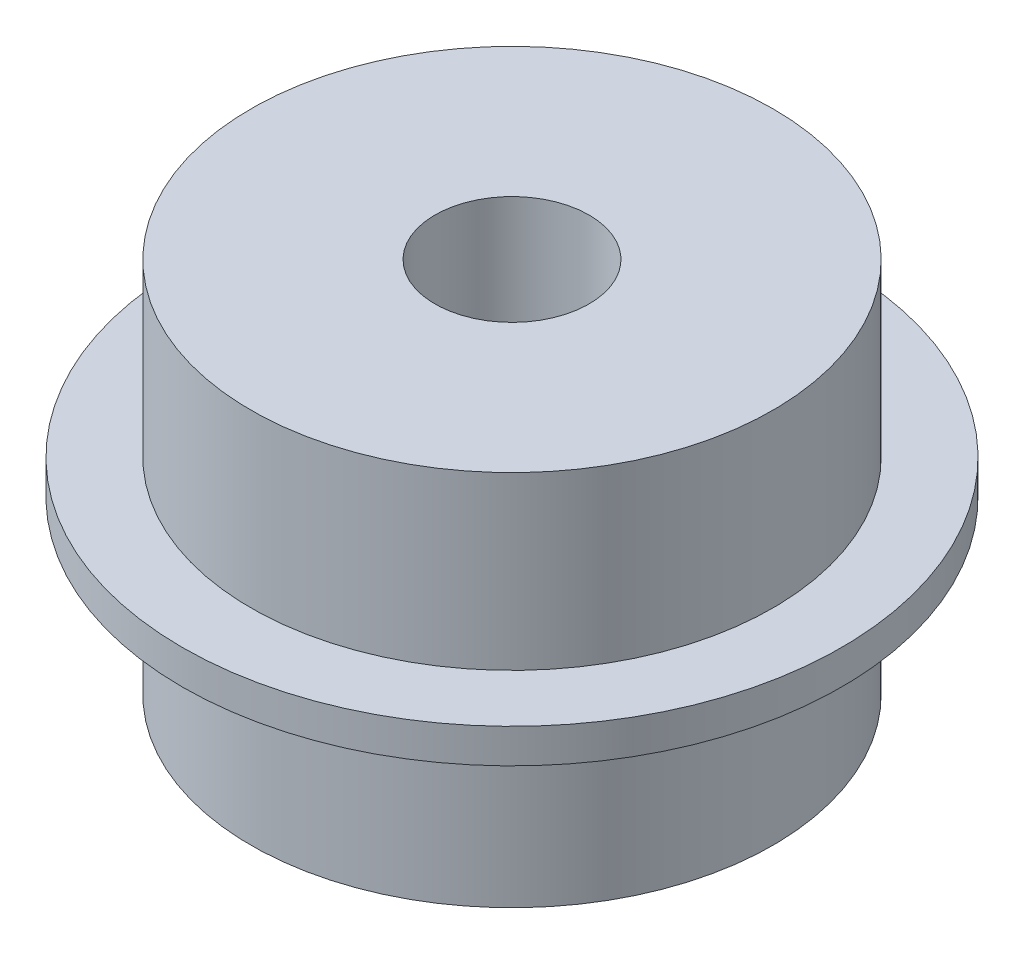
SolidWorks part; units mm, degrees
ref_plane "Front Plane" through (0, 0, 0) normal (0, 0, 1) x (1, 0, 0)
ref_plane "Top Plane" through (0, 0, 0) normal (0, 1, 0) x (1, 0, 0)
ref_plane "Right Plane" through (0, 0, 0) normal (1, 0, 0) x (0, 0, -1)
sketch "Sketch1" plane through (0, 0, 0) normal (0, 0, 1) x (1, 0, 0)
  line L0 (-2.25, -5.5) -> (-2.25, 5.5)
  line L13 (-2.25, 5.5) -> (-7.62, 5.5)
  line L14 (-7.62, 5.5) -> (-7.62, 0.5)
  line L15 (-7.62, 0.5) -> (-9.62, 0.5)
  line L16 (-9.62, 0.5) -> (-9.62, -0.5)
  line L17 (-9.62, -0.5) -> (-7.62, -0.5)
  line L18 (-7.62, -0.5) -> (-7.62, -5.5)
  line L19 (-7.62, -5.5) -> (-2.25, -5.5)
  line L20 (0, 0) -> (0, 11.906) construction
  point P4 (-7.5, 7.1485)
  point P10 (-2.25, 0)
  point P13 (-6.8292, -2.5)
  dimension "D1" = 2.25
  dimension "D2" = 7.62
  dimension "D3" = 1
  dimension "D4" = 5
  dimension "D5" = 2
revolve "Revolve1" add sketch "Sketch1" angle 360 about L20
